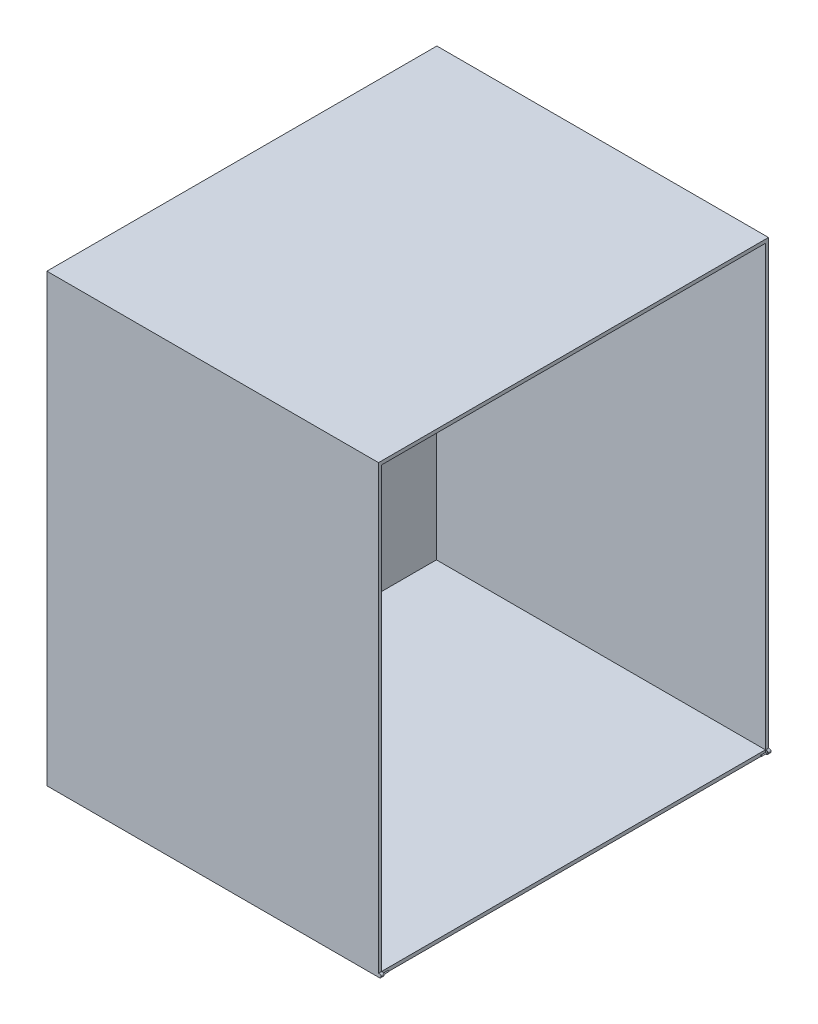
SolidWorks part; units mm, degrees
ref_plane "Front Plane" through (0, 0, 0) normal (0, 0, 1) x (1, 0, 0)
ref_plane "Top Plane" through (0, 0, 0) normal (0, 1, 0) x (1, 0, 0)
ref_plane "Right Plane" through (0, 0, 0) normal (1, 0, 0) x (0, 0, -1)
sketch "Sketch1" plane through (0, 0, 0) normal (0, 1, 0) x (1, 0, 0)
  line L1 (-302.4, 355.6) -> (302.4, 355.6)
  line L2 (-302.4, 355.6) -> (-302.4, -355.6)
  line L3 (-302.4, -355.6) -> (302.4, -355.6)
  line L4 (302.4, 355.6) -> (302.4, -355.6)
  line L5 (-302.4, 355.6) -> (302.4, -355.6) construction
  line L6 (-302.4, -355.6) -> (302.4, 355.6) construction
  point P0 (0, 0)
  dimension "D1" = 604.8
  dimension "D2" = 711.2
extrude "Boss-Extrude1" add sketch "Sketch1" along normal blind 812.8
sketch "Sketch2" plane through (302.4, 0, 0) normal (1, 0, 0) x (0, 0, -1)
  line L0 (0, 332.64) -> (0, -332.64) construction
  line L1 (-350, 806.4) -> (350, 806.4)
  line L2 (-350, 806.4) -> (-350, 6.4)
  line L3 (-350, 6.4) -> (350, 6.4)
  line L4 (350, 806.4) -> (350, 6.4)
  line L5 (-350, 806.4) -> (350, 6.4) construction
  line L6 (-350, 6.4) -> (350, 806.4) construction
  point P0 (0, 406.4)
  dimension "D1" = 700
  dimension "D2" = 800
extrude "Boss-Extrude2" add sketch "Sketch2" against normal blind 600
extrude "Cut-Extrude1" cut sketch "Sketch2<2>" against normal blind 600
sketch "Sketch2<2>" plane through (302.4, 0, 0) normal (1, 0, 0) x (0, 0, -1) same geometry as "Sketch2"
sketch "Sketch3" plane through (302.4, 0, 0) normal (1, 0, 0) x (0, 0, -1)
  line L0 (332.64, 0) -> (-332.64, 0) construction
  line L1 (-350, 6.4) -> (-355.6, 6.4)
  line L2 (-350, 6.4) -> (-350, 0)
  line L3 (-350, 0) -> (-355.6, 0)
  line L4 (-355.6, 6.4) -> (-355.6, 0)
  line L5 (-355.6, 812.8) -> (-355.6, 0) construction
  dimension "D1" = 6.4
extrude "Boss-Extrude3" add sketch "Sketch3" along normal blind 4.8
fillet "Fillet1" radius 3.2 2 edges at (307.2, 0, 352.8) (307.2, 6.4, 352.8)
sketch "Sketch4" plane through (0, 0, 350) normal (0, 0, -1) x (-1, 0, 0)
  line L0 (-302.4, 812.8) -> (-302.4, 0) construction
  line L1 (-304, 6.4) -> (-302.4, 6.4) construction
  circle A0 centre (-304.8, 3.2) radius 1
  point P3 (-304, 3.2)
  dimension "D1" = 2
  dimension "D2" = 2.4
  dimension "D3" = 3.2
extrude "Boss-Extrude4" add sketch "Sketch4" along normal blind 10
mirror "Mirror1" about plane through (0, 0, 0) normal (0, 0, 1) of "Fillet1", "Boss-Extrude3", "Boss-Extrude4"
